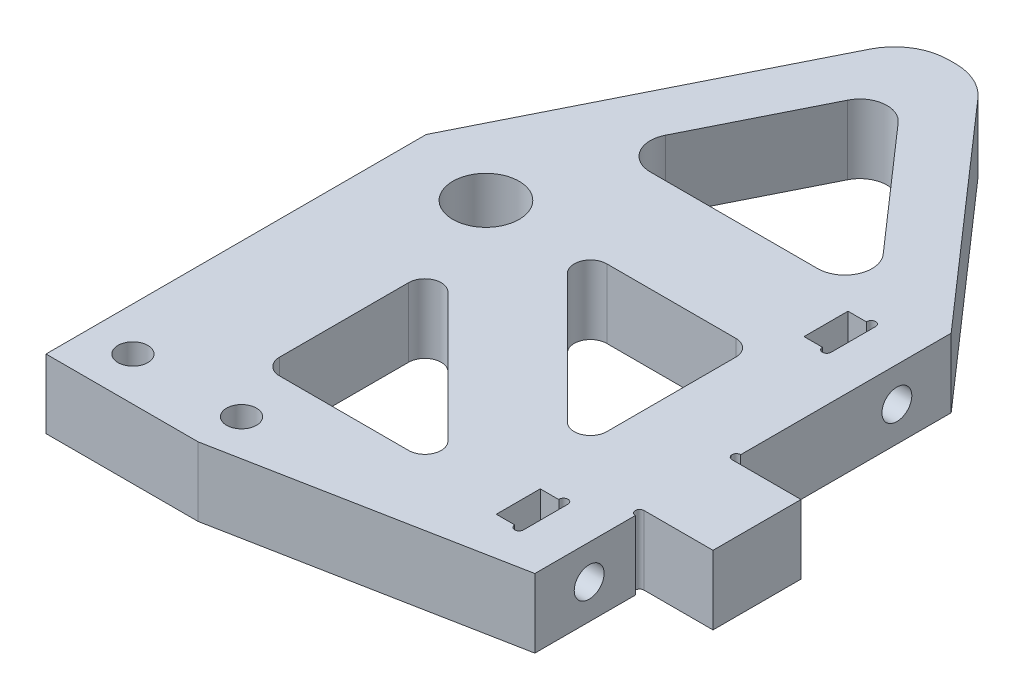
SolidWorks part; units mm, degrees
material "6061 Alloy"
ref_plane "Front Plane" through (0, 0, 0) normal (0, 0, 1) x (1, 0, 0)
ref_plane "Top Plane" through (0, 0, 0) normal (0, 1, 0) x (1, 0, 0)
ref_plane "Right Plane" through (0, 0, 0) normal (1, 0, 0) x (0, 0, -1)
sketch "Sketch1" plane through (0, 0, 0) normal (0, 1, 0) x (1, 0, 0)
  line L1 (-80, 0) -> (-80, 60)
  line L7 (0, 0) -> (-52, -10)
  line L8 (-52, -10) -> (-80, -10)
  line L9 (-80, -10) -> (-80, 0)
  line L10 (-80, 60) -> (-50, 120)
  line L11 (-50, 120) -> (-38, 120)
  line L12 (-38, 120) -> (0, 76.65)
  line L14 (0, 36.3) -> (12.7, 36.3)
  line L15 (12.7, 36.3) -> (12.7, 20.1)
  line L16 (12.7, 20.1) -> (0, 20.1)
  line L18 (0, 18.5) -> (0, 0)
  line L19 (0, 76.65) -> (0, 37.9)
  circle A0 centre (-64, 55) radius 6.1
  circle A3 centre (-72, -2) radius 2.75
  circle A4 centre (-52, -2) radius 2.75
  arc A5 (0, 20.1) -> (0, 18.5) centre (0, 19.3) ccw
  arc A6 (0, 36.3) -> (0, 37.9) centre (0, 37.1) cw
  dimension "D8" = 12.2
  dimension "D12" = 5.5
  dimension "D16" = 5.5
  dimension "D19" = 0.8
  dimension "D20" = 0.8
  dimension "D1" = 80
  dimension "D2" = 76.65
  dimension "D3" = 60
  dimension "D9" = 16
  dimension "D14" = 8
  dimension "D15" = 20
  dimension "D10" = 10
  dimension "D13" = 8
  dimension "D17" = 55
  dimension "D4" = 60
  dimension "D5" = 30
  dimension "D6" = 12
  dimension "D7" = 20.1
  dimension "D18" = 12.7
  dimension "D11" = 16.2
extrude "Boss-Extrude1" add sketch "Sketch1" along normal blind 12.7
fillet "Fillet1" radius 10 2 edges at (-38, 6.35, -120) (-50, 6.35, -120)
sketch "Sketch3" plane through (0, 12.7, 0) normal (0, 1, 0) x (1, 0, 0)
  line L5 (-11.545, 74.65) -> (-43.3521, 110.9352)
  line L6 (-43.3521, 110.9352) -> (-61.4947, 74.65)
  line L7 (-61.4947, 74.65) -> (-11.545, 74.65)
  line L8 (-58, 34.7574) -> (-58, 11)
  line L9 (-55, 8) -> (-31.2426, 8)
  line L10 (0, 76.65) -> (-35.0124, 116.5918) construction
  line L11 (-52.7639, 114.4721) -> (-80, 60) construction
  line L12 (-29.1213, 13.1213) -> (-52.8787, 36.8787)
  line L13 (-16, 29.2426) -> (-16, 53)
  line L14 (-19, 56) -> (-42.7574, 56)
  line L15 (-44.8787, 50.8787) -> (-21.1213, 27.1213)
  line L16 (-80, 60) -> (-80, -10) construction
  line L17 (-80, -10) -> (-52, -10) construction
  arc A0 (-16, 53) -> (-19, 56) centre (-19, 53) ccw
  arc A1 (-44.8787, 50.8787) -> (-42.7574, 56) centre (-42.7574, 53) cw
  arc A2 (-16, 29.2426) -> (-21.1213, 27.1213) centre (-19, 29.2426) cw
  arc A3 (-31.2426, 8) -> (-29.1213, 13.1213) centre (-31.2426, 11) ccw
  arc A4 (-55, 8) -> (-58, 11) centre (-55, 11) cw
  arc A5 (-58, 34.7574) -> (-52.8787, 36.8787) centre (-55, 34.7574) cw
  point P21 (-16, 56)
  point P24 (-50, 56)
  point P27 (-16, 22)
  point P30 (-24, 8)
  point P33 (-58, 8)
  point P36 (-58, 42)
  dimension "D14" = 3
  dimension "D1" = 10
  dimension "D2" = 10
  dimension "D3" = 10
  dimension "D4" = 10
  dimension "D5" = 2
  dimension "D6" = 22
  dimension "D7" = 18
  dimension "D8" = 34
  dimension "D9" = 34
  dimension "D10" = 64
  dimension "D11" = 32
  dimension "D12" = 34
  dimension "D13" = 34
extrude "Cut-Extrude1" cut sketch "Sketch3" against normal through all
fillet "Fillet2" radius 5 3 edges at (-43.3521, 6.35, -110.9352) (-11.545, 6.35, -74.65) (-61.4947, 6.35, -74.65)
sketch "Sketch4" plane through (0, 12.7, 0) normal (0, 1, 0) x (1, 0, 0)
  line L0 (0, 0) -> (0, 18.5) construction
  line L2 (-13, 14) -> (-13, 5.9)
  line L4 (-8, 14.1) -> (-8, 5.9)
  line L5 (-13, 14) -> (-9.5937, 14)
  line L6 (-13, 5.9) -> (-9.6, 5.9)
  line L7 (-13, 62.55) -> (-9.6, 62.55)
  line L8 (-8, 70.75) -> (-8, 62.55)
  line L9 (-13, 70.65) -> (-9.5937, 70.65)
  line L10 (-13, 70.65) -> (-13, 62.55)
  arc A0 (-8, 14.1) -> (-9.5937, 14) centre (-8.8, 14.1) ccw
  arc A1 (-8, 5.9) -> (-9.6, 5.9) centre (-8.8, 5.9) cw
  arc A2 (-8, 62.55) -> (-9.6, 62.55) centre (-8.8, 62.55) cw
  arc A3 (-8, 70.75) -> (-9.5937, 70.65) centre (-8.8, 70.75) ccw
  point P4 (-8, 10)
  point P12 (-8, 66.65)
  dimension "D5" = 0.8
  dimension "D1" = 10
  dimension "D3" = 8.2
  dimension "D4" = 5
  dimension "D7" = 10
  dimension "D6" = 2
extrude "Cut-Extrude2" cut sketch "Sketch4" against normal through all
sketch "Sketch6" plane through (-8, 0, 0) normal (-1, 0, 0) x (0, 0, 1)
  line L0 (-5.9, 0) -> (-5.9, 12.7) construction
  line L1 (-5.9, 12.7) -> (-14.1, 12.7) construction
  line L2 (-62.55, 0) -> (-62.55, 12.7) construction
  circle A0 centre (-10, 6.35) radius 2.75
  circle A1 centre (-66.65, 6.35) radius 2.75
  dimension "D2" = 5.5
  dimension "D5" = 5.5
  dimension "D1" = 4.1
  dimension "D3" = 6.35
  dimension "D4" = 4.1
extrude "Cut-Extrude3" cut sketch "Sketch6" against normal through all
equation "\"DriveMotorLength\"= 90mm"
equation "\"DriveMotorGap\"= 10mm"
equation "\"AluminumThickness\"= 0.5in"
equation "\"ChassisWidth\"= ( \"DriveMotorLength\" + \"AluminumThickness\" ) * 2 + \"DriveMotorGap\""
equation "\"RepeatMagnumHoleWidth\"= 19.05mm"
equation "\"MortiseWidth\"= 16mm"
equation "\"ChassisScrewThruHole\"= 5.5mm"
equation "\"D12@Sketch1\"=\"ChassisScrewThruHole\""
equation "\"D16@Sketch1\"=\"ChassisScrewThruHole\""
equation "\"MortiseSlotWidth\"= 16.2mm"
equation "\"D11@Sketch1\"=\"MortiseSlotWidth\""
equation "\"Dogbone\"= 0.8mm"
equation "\"D19@Sketch1\"=\"Dogbone\""
equation "\"D20@Sketch1\"=\"Dogbone\""
equation "\"D5@Sketch4\"=\"Dogbone\""
equation "\"D2@Sketch6\"=\"ChassisScrewThruHole\""
equation "\"D5@Sketch6\"=\"ChassisScrewThruHole\""
